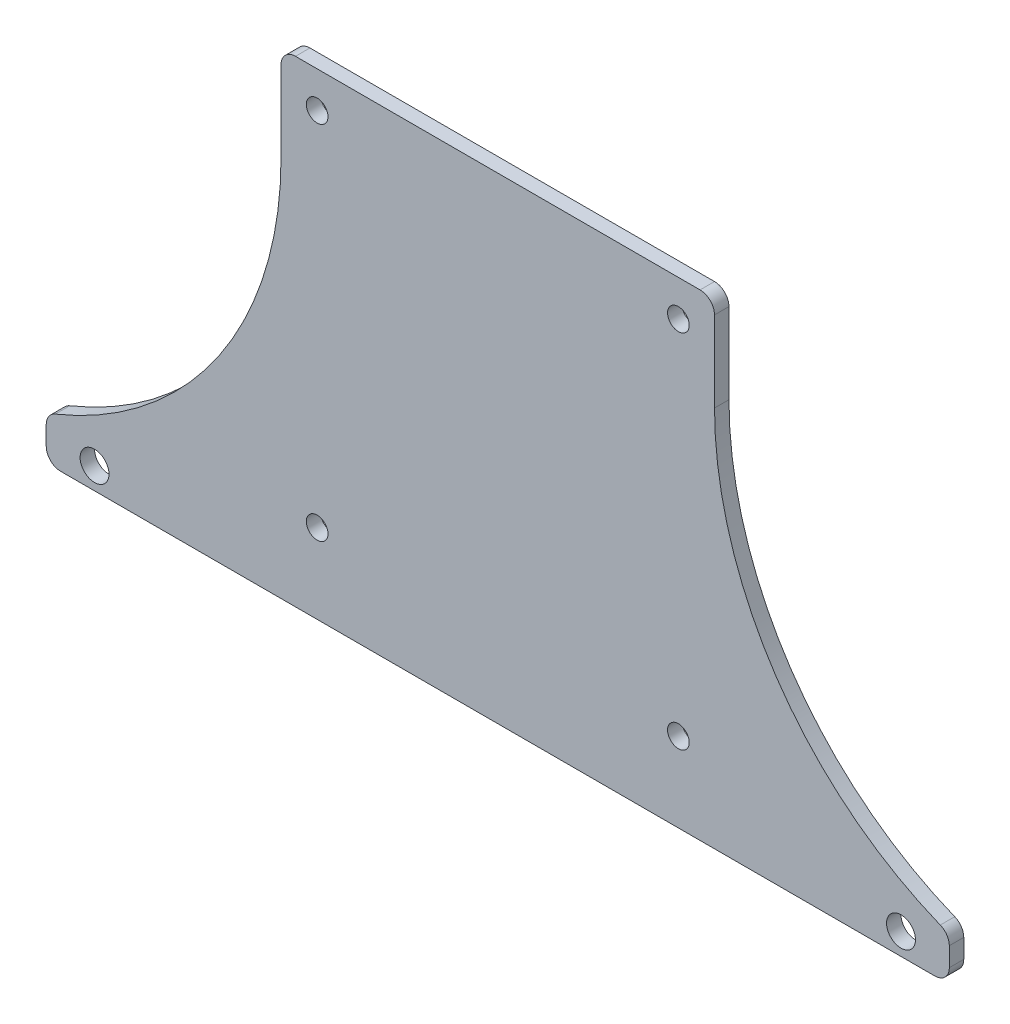
SolidWorks part; units mm, degrees
ref_plane "前视基准面" through (0, 0, 0) normal (0, 0, 1) x (1, 0, 0)
ref_plane "上视基准面" through (0, 0, 0) normal (0, 1, 0) x (1, 0, 0)
ref_plane "右视基准面" through (0, 0, 0) normal (1, 0, 0) x (0, 0, -1)
other "Configuration Table"
sketch "草图1" plane through (0, 0, 0) normal (0, 0, 1) x (1, 0, 0)
  line L0 (0, 0) -> (60, 60) construction
  line L5 (0, 0) -> (60, 0)
  line L6 (0, 0) -> (0, 60)
  line L7 (0, 60) -> (60, 60)
  line L8 (60, 0) -> (60, 60)
  line L9 (60, 0) -> (0, 60) construction
  line L10 (30, 30) -> (30, 38.6732) construction
  line L11 (30, 30) -> (23.4143, 30) construction
  circle A0 centre (5, 55) radius 1.5
  circle A1 centre (55, 55) radius 1.5
  circle A2 centre (55, 5) radius 1.5
  circle A3 centre (5, 5) radius 1.5
  point P4 (30, 30)
  dimension "D3" = 3
  dimension "D1" = 60
  dimension "D2" = 60
  dimension "D4" = 50
extrude "凸台-拉伸1" add sketch "草图1" along normal blind 2
sketch "草图2" plane through (0, 0, 2) normal (0, 0, 1) x (1, 0, 0)
  line L0 (30, 0) -> (30, 12.4949) construction
  line L2 (0, 0) -> (60, 0) construction
  line L3 (30, 0) -> (30, -6) construction
  line L8 (-32.5, -6) -> (92.5, -6)
  line L9 (-32.5, -6) -> (-32.5, 0)
  line L10 (-32.5, 0) -> (92.5, 0)
  line L11 (92.5, -6) -> (92.5, 0)
  circle A0 centre (-25.815, -3) radius 2
  circle A1 centre (85.815, -3) radius 2
  dimension "D3" = 55.815
  dimension "D5" = 4
  dimension "D1" = 125
  dimension "D2" = 6
  dimension "D4" = 3
extrude "凸台-拉伸2" add sketch "草图2" against normal blind 2
fillet "圆角1" radius 50 2 edges at (60, 0, 1) (0, 0, 1)
fillet "圆角2" radius 2 6 edges at (0, 60, 1) (60, 60, 1) (92.5, -6, 1) (92.5, 0, 1) (-32.5, -6, 1) (-32.5, 0, 1)
